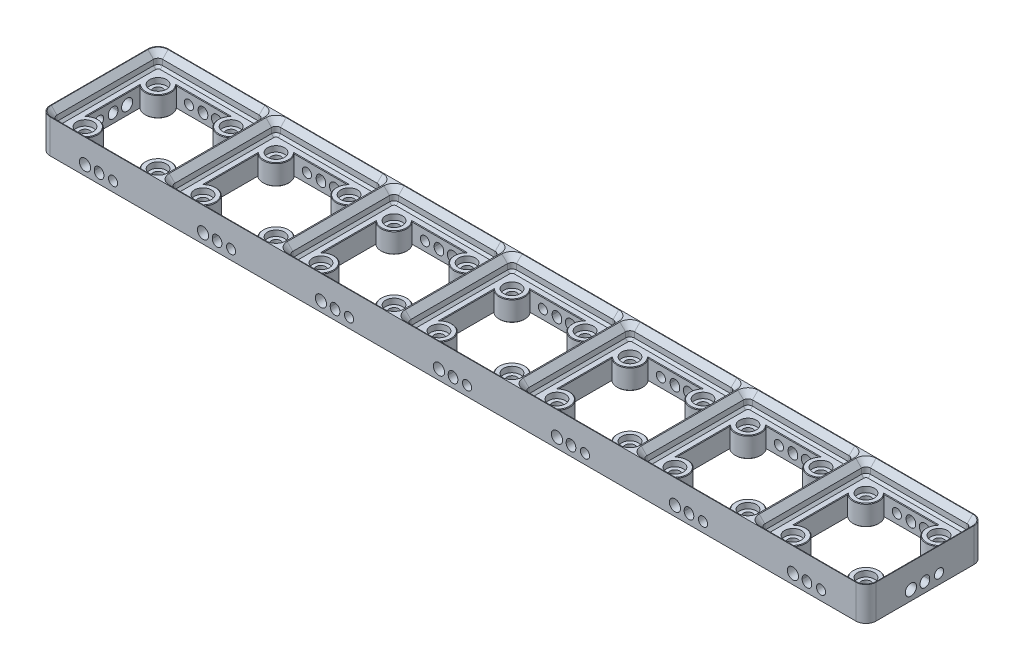
SolidWorks part; units mm, degrees
ref_plane "Front Plane" through (0, 0, 0) normal (0, 0, 1) x (1, 0, 0)
ref_plane "Top Plane" through (0, 0, 0) normal (0, 1, 0) x (1, 0, 0)
ref_plane "Right Plane" through (0, 0, 0) normal (1, 0, 0) x (0, 0, -1)
ref_axis "Axis1" through (0, -6.6, 0) along (0, 1, 0)
sketch "Sketch1" plane through (0, 0, 0) normal (0, 1, 0) x (1, 0, 0)
  line L1 (147, 21) -> (-147, 21)
  line L2 (147, 21) -> (147, -21)
  line L3 (147, -21) -> (-147, -21)
  line L4 (-147, 21) -> (-147, -21)
  line L5 (0, -21) -> (0, 21) construction
  line L6 (147, 0) -> (-147, 0) construction
  point P0 (0, 0)
  dimension "WIDTH" = 42
  dimension "LENGTH" = 294
extrude "MAIN BODY" add sketch "Sketch1" along normal mid plane 12
sketch "Sketch2" plane through (0, 6, 0) normal (0, 1, 0) x (1, 0, 0)
  line L0 (147, -21) -> (147, 21) construction
  line L1 (147, -21) -> (105, -21) construction
  line L2 (147, -21) -> (147, 21) construction
  line L3 (147, 21) -> (105, 21) construction
  line L4 (105, -21) -> (105, 21) construction
  line L5 (126, 21) -> (126, -21) construction
  line L6 (147, 0) -> (105, 0) construction
  line L7 (-147, -21) -> (147, -21) construction
  line L13 (143.2, -18.8) -> (108.8, -18.8)
  line L14 (144.8, -17.2) -> (144.8, 17.2)
  line L15 (143.2, 18.8) -> (108.8, 18.8)
  line L16 (107.2, -17.2) -> (107.2, 17.2)
  line L17 (126, 18.8) -> (126, -18.8) construction
  line L18 (144.8, 0) -> (107.2, 0) construction
  arc A4 (108.8, -18.8) -> (107.2, -17.2) centre (108.8, -17.2) cw
  arc A5 (143.2, -18.8) -> (144.8, -17.2) centre (143.2, -17.2) ccw
  arc A6 (144.8, 17.2) -> (143.2, 18.8) centre (143.2, 17.2) ccw
  arc A7 (108.8, 18.8) -> (107.2, 17.2) centre (108.8, 17.2) ccw
  point P0 (126, 0)
  point P12 (126, 0)
  point P24 (144.8, 18.8)
  point P27 (107.2, 18.8)
  dimension "D3" = 1.6
  dimension "D1" = 42
  dimension "D2" = 37.6
extrude "GRID CUT OUT" cut sketch "Sketch2" against normal blind 4.75
chamfer "GRID TOP CHANFER" distance 2 angle 45 8 edges at (126, 6, 18.8) (144.3314, 6, 18.3314) (107.6686, 6, 18.3314) (144.8, 6, 0) (107.2, 6, 0) (144.3314, 6, -18.3314) (107.6686, 6, -18.3314) (126, 6, -18.8)
chamfer "GRID BOTTOM CHANFER" distance 0.8 angle 45 8 edges at (126, 1.25, 18.8) (144.3314, 1.25, 18.3314) (107.6686, 1.25, 18.3314) (144.8, 1.25, 0) (107.2, 1.25, 0) (144.3314, 1.25, -18.3314) (107.6686, 1.25, -18.3314) (126, 1.25, -18.8)
hole_wizard "SCREW HOLES" positions "Sketch3" profile "Sketch4" countersink size "M3" standard "ANSI Metric" end condition through all
sketch "Sketch3" plane through (0, -6, 0) normal (0, -1, 0) x (-1, 0, 0)
  line L1 (-147, 21) -> (-105, 21)
  line L2 (-147, 21) -> (-147, -21)
  line L3 (-147, -21) -> (-105, -21)
  line L4 (-105, 21) -> (-105, -21)
  line L5 (-126, -21) -> (-126, 21) construction
  line L6 (-147, 0) -> (-105, 0) construction
  line L7 (147, -21) -> (-147, -21) construction
  line L8 (-147, -21) -> (-147, 21) construction
  line L9 (-139, -13) -> (-113, -13)
  line L10 (-113, 13) -> (-113, -13)
  line L11 (-139, 13) -> (-113, 13)
  line L12 (-139, 13) -> (-139, -13)
  point P0 (-113, -13)
  point P2 (-139, -13)
  point P4 (-139, 13)
  point P6 (-113, 13)
  dimension "D1" = 42
  dimension "D2" = 26
sketch "Sketch4" plane through (113, -6, 13) normal (1, 0, 0) x (0, 0, -1)
  line L0 (0, 0) -> (0, 12)
  line L1 (0, 12) -> (1.7, 12)
  line L2 (1.7, 12) -> (1.7, 1.66)
  line L3 (1.7, 1.66) -> (3.36, 0)
  line L5 (3.36, 0) -> (0, 0)
  line L6 (-1.7, 1.66) -> (-3.36, 0) construction
  line L11 (0, -6.35) -> (0, 107.95) construction
  dimension "Thru Hole Dia." = 3.4
  dimension "Thru Hole Depth" = 12
  dimension "Near C'Sink Dia." = 6.72
  dimension "Near C'Sink Angle" = 90
sketch "Sketch5" plane through (0, 1.25, 0) normal (0, 1, 0) x (1, 0, 0)
  circle A0 centre (113, -13) radius 3
  circle A1 centre (113, 13) radius 3
  circle A2 centre (139, 13) radius 3
  circle A3 centre (139, -13) radius 3
  dimension "D1" = 6
extrude "MAGNET HOLES" cut sketch "Sketch5" against normal blind 2
sketch "Sketch9" plane through (0, 1.25, 0) normal (0, 1, 0) x (1, 0, 0)
  line L0 (116.4871, -16) -> (135.5129, -16)
  line L1 (142, -9.5129) -> (142, 9.5129)
  line L2 (135.5129, 16) -> (116.4871, 16)
  line L3 (110, 9.5129) -> (110, -9.5129)
  line L4 (108.8, -18) -> (143.2, -18)
  line L5 (144, -17.2) -> (144, 17.2)
  line L6 (143.2, 18) -> (108.8, 18)
  line L7 (108, 17.2) -> (108, -17.2)
  line L8 (108.8, -18) -> (143.2, -18) construction
  line L9 (144, -17.2) -> (144, 17.2) construction
  line L10 (143.2, 18) -> (108.8, 18) construction
  line L11 (108, 17.2) -> (108, -17.2) construction
  line L12 (110, -16) -> (142, -16) construction
  line L13 (142, -16) -> (142, 16) construction
  line L14 (110, 16) -> (110, -16) construction
  line L15 (142, 16) -> (110, 16) construction
  line L16 (142, 0) -> (110, 0) construction
  line L17 (126, -16) -> (126, 16) construction
  circle A1 centre (113, -13) radius 3
  circle A2 centre (113, -13) radius 3 construction
  circle A5 centre (139, -13) radius 3 construction
  circle A7 centre (139, -13) radius 3 construction
  arc A12 (108, -17.2) -> (108.8, -18) centre (108.8, -17.2) ccw
  arc A13 (143.2, -18) -> (144, -17.2) centre (143.2, -17.2) ccw
  arc A14 (144, 17.2) -> (143.2, 18) centre (143.2, 17.2) ccw
  arc A15 (108.8, 18) -> (108, 17.2) centre (108.8, 17.2) ccw
  arc A16 (108, -17.2) -> (108.8, -18) centre (108.8, -17.2) ccw construction
  arc A17 (143.2, -18) -> (144, -17.2) centre (143.2, -17.2) ccw construction
  arc A18 (144, 17.2) -> (143.2, 18) centre (143.2, 17.2) ccw construction
  arc A19 (108.8, 18) -> (108, 17.2) centre (108.8, 17.2) ccw construction
  arc A20 (142, -9.5129) -> (135.5129, -16) centre (139, -13) ccw
  arc A21 (116.4871, -16) -> (110, -9.5129) centre (113, -13) ccw
  arc A22 (110, 9.5129) -> (116.4871, 16) centre (113, 13) ccw
  arc A23 (135.5129, 16) -> (142, 9.5129) centre (139, 13) ccw
  circle A24 centre (139, -13) radius 4.6 construction
  circle A25 centre (113, -13) radius 4.6 construction
  arc A29 (142, 16) -> (142, 16) centre (142, 16) ccw construction
  arc A30 (110, 16) -> (110, 16) centre (110, 16) ccw construction
  arc A31 (110, -16) -> (110, -16) centre (110, -16) ccw construction
  arc A32 (142, -16) -> (142, -16) centre (142, -16) ccw construction
  point P39 (126, 0)
  dimension "D2" = 2
  dimension "D1" = 0
  dimension "D3" = 0
  dimension "D5" = 1.6
extrude "WEIGHT REDUCTION" cut sketch "Sketch9" against normal through all
chamfer "WEIGHT REDUCTION CHAMFER" distance 0.2 angle 45 16 edges at (135.7473, 1.25, 9.7473) (142, 1.25, 0) (135.7473, 1.25, -9.7473) (126, 1.25, -16) (116.2527, 1.25, -9.7473) (110, 1.25, 0) (116.2527, 1.25, 9.7473) (126, 1.25, 16) (110, -6, 0) (116.2527, -6, -9.7473) (126, -6, -16) (135.7473, -6, -9.7473) (142, -6, 0) (135.7473, -6, 9.7473) (126, -6, 16) (116.2527, -6, 9.7473)
pattern_linear "GRID LENGTH PATTERN" count 7 spacing 42 along (-1, 0, 0) of "GRID CUT OUT", "GRID TOP CHANFER", "GRID BOTTOM CHANFER", "SCREW HOLES", "MAGNET HOLES", "WEIGHT REDUCTION", "WEIGHT REDUCTION CHAMFER"
pattern_linear "GRID WIDTH PATTERN" [suppressed] count 1 spacing 42 of bodies 249
sketch "Sketch29" plane through (0, 0, 21) normal (0, 0, 1) x (1, 0, 0)
  line L0 (127.7, -2.7) -> (127.7, -2.3)
  line L1 (124.3, -2.3) -> (124.3, -2.7)
  line L2 (121, -2.5) -> (131, -2.5) construction
  line L3 (126, -2.3) -> (126, -2.7) construction
  line L4 (126, 0) -> (126, -2.3) construction
  line L5 (-147, -6) -> (147, -6) construction
  line L6 (126, 0) -> (147, 0)
  line L8 (147, 6) -> (147, -6) construction
  circle A0 centre (131, -2.5) radius 1.632
  arc A1 (127.7, -2.3) -> (124.3, -2.3) centre (126, -2.3) ccw
  arc A2 (124.3, -2.7) -> (127.7, -2.7) centre (126, -2.7) ccw
  circle A3 centre (121, -2.5) radius 2
  point P13 (126, -0.6)
  point P14 (126, -2.5)
  point P16 (126, -4.4)
  point P17 (126, -2.5)
  dimension "D1" = 4
  dimension "D2" = 3.2639
  dimension "D3" = 3.4
  dimension "D4" = 10
  dimension "D5" = 21
  dimension "D6" = 3.8
  dimension "D7" = 3.5
extrude "LENGTH HOLES" cut sketch "Sketch29" against normal blind 10 contours A3 | L1 A2 L0 A1 | A0 region at (126, -2.5, 21) region at (131, -2.5, 21) region at (121, -2.5, 21)
sketch "Sketch28" plane through (147, 0, 0) normal (1, 0, 0) x (0, 0, -1)
  line L0 (1.7, -2.7) -> (1.7, -2.3)
  line L1 (-1.7, -2.3) -> (-1.7, -2.7)
  line L2 (-5, -2.5) -> (5, -2.5) construction
  line L3 (0, -2.3) -> (0, -2.7) construction
  line L4 (0, 0) -> (0, -2.3) construction
  line L5 (-21, -6) -> (21, -6) construction
  line L6 (0, 0) -> (-21, 0) construction
  line L7 (-21, 6) -> (-21, -6) construction
  circle A0 centre (5, -2.5) radius 1.6319
  arc A1 (1.7, -2.3) -> (-1.7, -2.3) centre (0, -2.3) ccw
  arc A2 (-1.7, -2.7) -> (1.7, -2.7) centre (0, -2.7) ccw
  circle A3 centre (-5, -2.5) radius 2
  point P13 (0, -0.6)
  point P14 (0, -2.5)
  point P16 (0, -4.4)
  point P17 (0, -2.5)
  dimension "D1" = 4
  dimension "D2" = 3.2639
  dimension "D3" = 3.4
  dimension "D4" = 10
  dimension "D5" = 3.5
  dimension "D6" = 3.8
  dimension "D7" = 21
extrude "WIDTH HOLES" cut sketch "Sketch28" against normal blind 10 and the other way through all
pattern_linear "HOLE LENGTH PATTERN" count 7 spacing 42 along (-1, 0, 0) of "LENGTH HOLES"
pattern_linear "HOLE WIDTH PATTERN" [suppressed] count 1 spacing 42 of bodies 254
pattern_circular "ROTATE LENGTH HOLES" [suppressed] count 2 every 180 about axis through (0, -6.6, 0) along (0, 1, 0) of bodies 179
pattern_circular "ROTATE LENGTH PATTERN HOLES" count 2 every 180 about axis through (0, -6.6, 0) along (0, 1, 0) of "HOLE LENGTH PATTERN"
pattern_circular "ROTATE WIDTH HOLES" count 2 every 180 about axis through (0, -6.6, 0) along (0, 1, 0) of "WIDTH HOLES"
pattern_circular "ROTATE WIDTH PATTEN HOLES" [suppressed] count 2 every 180 about axis through (0, -6.6, 0) along (0, 1, 0) of bodies 257
fillet "FILLET CORNERS" radius 3.6 4 edges at (-147, 0, -21) (147, 0, -21) (147, 0, 21) (-147, 0, 21)
equation "\"LENGTH\"= 7"
equation "\"WIDTH\"= 1"
equation "\"LENGTH@Sketch1\"= \"LENGTH\" * 42"
equation "\"D1@GRID LENGTH PATTERN\"= \"LENGTH\""
equation "\"D1@HOLE LENGTH PATTERN\"=\"LENGTH\""
equation "\"D1@HOLE WIDTH PATTERN\"=\"WIDTH\""
equation "\"GRID LENGTH PATTERN\"= IIF ( \"LENGTH\" > 1 ,  unsuppressed  ,  suppressed  ) "
equation "\"HOLE LENGTH PATTERN\"= IIF ( \"LENGTH\" > 1 ,  unsuppressed  ,  suppressed  ) "
equation "\"GRID WIDTH PATTERN\"= IIF ( \"WIDTH\" > 1 , \"unsuppressed\" , \"suppressed\" )"
equation "\"HOLE WIDTH PATTERN\"= IIF ( \"WIDTH\" > 1 , \"unsuppressed\" , \"suppressed\" )"
equation "\"WIDTH@Sketch1\"= \"WIDTH\" * 42"
equation "\"D1@GRID WIDTH PATTERN\"=\"WIDTH\""
equation "\"ROTATE LENGTH HOLES\"= IIF ( \"LENGTH\" > 1 , \"suppressed\" , \"unsuppressed\" )"
equation "\"ROTATE LENGTH PATTERN HOLES\"= IIF ( \"LENGTH\" > 1 , \"unsuppressed\" , \"suppressed\" )"
equation "\"ROTATE WIDTH HOLES\"= IIF ( \"WIDTH\" > 1 , \"suppressed\" , \"unsuppressed\" )"
equation "\"ROTATE WIDTH PATTEN HOLES\"= IIF ( \"WIDTH\" > 1 , \"unsuppressed\" , \"suppressed\" )"
